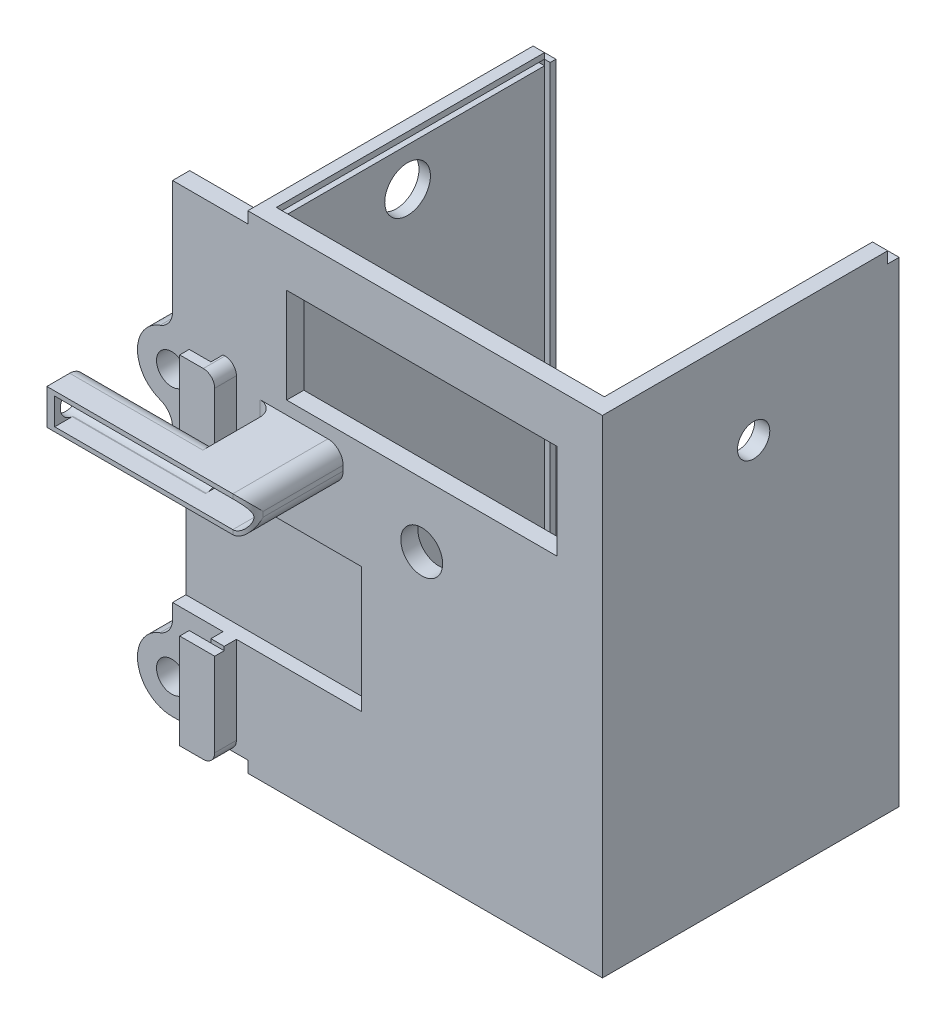
SolidWorks part; units mm, degrees
ref_plane "Alzado" through (0, 0, 0) normal (0, 0, 1) x (1, 0, 0)
ref_plane "Planta" through (0, 0, 0) normal (0, 1, 0) x (1, 0, 0)
ref_plane "Vista lateral" through (0, 0, 0) normal (1, 0, 0) x (0, 0, -1)
sketch "Croquis1" plane through (0, 0, 0) normal (0, 0, 1) x (1, 0, 0)
  circle A0 centre (-36.5282, 48.197) radius 4
  circle A1 centre (-36.5282, -21.803) radius 4
  circle A2 centre (-36.5282, 48.197) radius 9
  circle A3 centre (-36.5282, -21.803) radius 9
  dimension "D2" = 8
  dimension "D3" = 70
  dimension "D4" = 5
extrude "Saliente-Extruir1" add sketch "Croquis1" along normal blind 7
sketch "Croquis2" plane through (0, 0, 7) normal (0, 0, 1) x (1, 0, 0)
  line L0 (-18.6932, 21.2688) -> (-1.627, 21.2688) construction
  line L1 (-36.3068, 91.2688) -> (73.6932, 91.2688)
  line L2 (-36.3068, 91.2688) -> (-36.3068, -30.8003)
  line L3 (-36.3068, -30.8003) -> (73.6932, -30.8003)
  line L4 (73.6932, 91.2688) -> (73.6932, -30.8003)
  circle A2 centre (-36.5282, 48.197) radius 9
  circle A3 centre (-36.5282, -21.803) radius 9
  circle A4 centre (-36.5282, -21.803) radius 9 construction
  circle A5 centre (-36.5282, 48.197) radius 9 construction
  circle M7 centre (-36.5282, 48.197) radius 9
  dimension "D1" = 110
  dimension "D2" = 70
extrude "Saliente-Extruir2" add sketch "Croquis2" against normal blind 4.5 contours A3 L3 L4 L1 L2 M7
sketch "Croquis4" plane through (0, 0, 7) normal (0, 0, 1) x (1, 0, 0)
  line L1 (-23.0282, 58.197) -> (-19.5282, 58.197)
  line L2 (-23.0282, 58.197) -> (-23.0282, -30.8003)
  line L3 (-23.0282, -30.8003) -> (-19.5282, -30.8003)
  line L4 (-19.5282, 58.197) -> (-19.5282, -30.8003)
  line L5 (-36.3068, -30.8003) -> (73.6932, -30.8003) construction
  circle A0 centre (-36.5282, 48.197) radius 4 construction
  dimension "D2" = 10
  dimension "D1" = 13.5
  dimension "D4" = 3.5
extrude "Saliente-Extruir3" add sketch "Croquis4" along normal blind 3.2
sketch "Croquis3" plane through (0, 0, 7) normal (0, 0, 1) x (1, 0, 0)
  line L1 (-36.6357, 28.197) -> (13.3643, 28.197)
  line L2 (-36.6357, 28.197) -> (-36.6357, -4.803)
  line L3 (-36.6357, -4.803) -> (13.3643, -4.803)
  line L4 (13.3643, 28.197) -> (13.3643, -4.803)
  circle A0 centre (-36.5282, 48.197) radius 4 construction
  circle A2 centre (-36.5282, -21.803) radius 4 construction
  dimension "D3" = 50
  dimension "D1" = 17
  dimension "D2" = 20
extrude "Cortar-Extruir1" cut sketch "Croquis3" against normal blind 3.5 and the other way blind 13.5
sketch "Croquis5" plane through (0, 0, 10.2) normal (0, 0, 1) x (1, 0, 0)
  line L0 (-19.5282, -30.8003) -> (-19.5282, -4.803) construction
  line L1 (-28.7282, 58.197) -> (-19.5282, 58.197)
  line L2 (-28.7282, 58.197) -> (-28.7282, 29.197)
  line L3 (-28.7282, 29.197) -> (-19.5282, 29.197)
  line L4 (-19.5282, 58.197) -> (-19.5282, 29.197)
  line L5 (-28.7282, -5.803) -> (-19.5282, -5.803)
  line L6 (-28.7282, -5.803) -> (-28.7282, -30.8003)
  line L7 (-28.7282, -30.8003) -> (-19.5282, -30.8003)
  line L8 (-19.5282, -5.803) -> (-19.5282, -30.8003)
  line L10 (-23.0282, 28.197) -> (-36.3068, 28.197) construction
  line L11 (-36.3068, -4.803) -> (-23.0282, -4.803) construction
  line L12 (-23.0282, -30.8003) -> (-19.5282, -30.8003) construction
  line L16 (-19.5282, 58.197) -> (-23.0282, 58.197) construction
  dimension "D1" = 9.2
  dimension "D2" = 9.2
  dimension "D3" = 1
  dimension "D5" = 1
extrude "Saliente-Extruir4" add sketch "Croquis5" along normal blind 2.5
fillet "Redondeo1" radius 3 2 edges at (-19.5282, -30.8003, 9.85) (-19.5282, 58.197, 9.85)
fillet "Redondeo2" radius 5 2 edges at (-36.3068, -12.8057, 4.75) (-36.3068, 39.1997, 4.75)
sketch "Croquis6" plane through (0, 0, 7) normal (0, 0, 1) x (1, 0, 0)
  line L1 (-11.3068, 86.2688) -> (68.6932, 86.2688) construction
  line L2 (-11.3068, 86.2688) -> (-11.3068, 50.2688) construction
  line L3 (-11.3068, 50.2688) -> (68.6932, 50.2688) construction
  line L4 (68.6932, 86.2688) -> (68.6932, 50.2688) construction
  line L5 (-36.3068, 91.2688) -> (73.6932, 91.2688) construction
  line L11 (73.6932, 91.2688) -> (73.6932, -30.8003) construction
  line L13 (-6.3068, 81.2688) -> (64.6932, 81.2688)
  line L14 (-6.3068, 81.2688) -> (-6.3068, 56.2688)
  line L15 (-6.3068, 56.2688) -> (64.6932, 56.2688)
  line L16 (64.6932, 81.2688) -> (64.6932, 56.2688)
  point P13 (68.6932, 68.2688)
  dimension "D1" = 80
  dimension "D2" = 36
  dimension "D3" = 5
  dimension "D4" = 5
  dimension "D5" = 71
  dimension "D6" = 25
  dimension "D7" = 5
  dimension "D8" = 4
extrude "Cortar-Extruir2" cut sketch "Croquis6" against normal through all
sketch "Croquis7" plane through (0, 0, 0) normal (0, 0, -1) x (-1, 0, 0)
  line L0 (-64.6932, 56.2688) -> (-64.6932, 81.2688) construction
  line L1 (-68.1932, 75.7696) -> (-64.6932, 75.7696)
  line L2 (-68.1932, 75.7696) -> (-68.1932, 61.7696)
  line L3 (-68.1932, 61.7696) -> (-64.6932, 61.7696)
  line L4 (-64.6932, 75.7696) -> (-64.6932, 61.7696)
  dimension "D1" = 3.5
  dimension "D2" = 14
extrude "Cortar-Extruir3" cut sketch "Croquis7" against normal blind 5.5
sketch "Croquis8" plane through (0, 0, 0) normal (0, 0, -1) x (-1, 0, 0)
  line L0 (-64.6932, 81.2688) -> (6.3068, 81.2688) construction
  line L1 (-70.5004, 87.2688) -> (9.4996, 87.2688)
  line L2 (-70.5004, 87.2688) -> (-70.5004, 51.2688)
  line L3 (-70.5004, 51.2688) -> (9.4996, 51.2688)
  line L4 (9.4996, 87.2688) -> (9.4996, 51.2688)
  circle A0 centre (-68.5004, 85.2688) radius 1
  circle A1 centre (7.4996, 85.2688) radius 1
  circle A2 centre (7.4996, 53.2688) radius 1
  circle A3 centre (-68.5004, 53.2688) radius 1
  dimension "D4" = 2
  dimension "D5" = 2
  dimension "D6" = 2
  dimension "D1" = 36
  dimension "D2" = 80
  dimension "D3" = 6
  dimension "D7" = 2
  dimension "D8" = 2
extrude "Cortar-Extruir4" cut sketch "Croquis8" against normal blind 5 contours A0 | A1 | A2 | A3
sketch "Croquis9" plane through (73.6932, 0, 0) normal (1, 0, 0) x (0, 0, -1)
  line L0 (-7, 91.2688) -> (-7, -30.8003) construction
  line L1 (-7, 91.2688) -> (68, 91.2688)
  line L2 (-7, 91.2688) -> (-7, -30.8003)
  line L3 (-7, -30.8003) -> (68, -30.8003)
  line L4 (68, 91.2688) -> (68, -30.8003)
  line L5 (-2.5, 91.2688) -> (-7, 91.2688) construction
  line L6 (-2.5, -30.8003) -> (-7, -30.8003) construction
  dimension "D1" = 75
extrude "Saliente-Extruir5" add sketch "Croquis9" along normal blind 3 and the other way blind 1
sketch "Croquis10" plane through (0, -30.8003, 0) normal (0, -1, 0) x (1, 0, 0)
  line L0 (-22.5282, 7) -> (76.6932, 7) construction
  line L1 (-16.5282, 7) -> (-13.5282, 7)
  line L2 (-16.5282, 7) -> (-16.5282, -68)
  line L3 (-16.5282, -68) -> (-13.5282, -68)
  line L4 (-13.5282, 7) -> (-13.5282, -68)
  line L5 (-19.5282, 12.7) -> (-19.5282, 7) construction
  line L6 (76.6932, -68) -> (72.6932, -68) construction
  dimension "D1" = 3
  dimension "D2" = 3
extrude "Saliente-Extruir6" add sketch "Croquis10" against normal through all
sketch "Croquis11" plane through (0, -30.8003, 0) normal (0, -1, 0) x (1, 0, 0)
  line L1 (-16.5282, 7) -> (76.6932, 7)
  line L2 (-16.5282, 7) -> (-16.5282, -68)
  line L3 (-16.5282, -68) -> (76.6932, -68)
  line L4 (76.6932, 7) -> (76.6932, -68)
  line L5 (-22.5282, 7) -> (76.6932, 7) construction
  line L6 (-16.5282, 2.5) -> (-16.5282, -68) construction
extrude "Saliente-Extruir7" add sketch "Croquis11" along normal blind 3
sketch "Croquis12" plane through (72.6932, 0, 0) normal (-1, 0, 0) x (0, 0, 1)
  line L0 (-68, -30.8003) -> (-68, 91.2688) construction
  line L1 (-63, 43.1997) -> (-9, 43.1997) construction
  line L2 (-63, 43.1997) -> (-63, -25.8003) construction
  line L3 (-63, -25.8003) -> (-9, -25.8003) construction
  line L4 (-9, 43.1997) -> (-9, -25.8003) construction
  line L5 (2.5, -30.8003) -> (-68, -30.8003) construction
  circle A0 centre (-61, 29.1997) radius 2
  circle A1 centre (-11, 27.6997) radius 2
  circle A2 centre (-55, -23.8003) radius 2
  circle A3 centre (-27, -23.8003) radius 2
  circle A4 centre (-61, 29.1997) radius 1
  circle A5 centre (-11, 27.6997) radius 1
  circle A6 centre (-55, -23.8003) radius 1
  circle A7 centre (-27, -23.8003) radius 1
  dimension "D5" = 4
  dimension "D6" = 2
  dimension "D7" = 2
  dimension "D11" = 15.5
  dimension "D13" = 2
  dimension "D1" = 54
  dimension "D2" = 69
  dimension "D3" = 5
  dimension "D4" = 5
  dimension "D8" = 2
  dimension "D9" = 8
  dimension "D10" = 18
  dimension "D12" = 14
extrude "Saliente-Extruir8" add sketch "Croquis12" along normal blind 4
sketch "Croquis13" plane through (68.6932, 0, 0) normal (-1, 0, 0) x (0, 0, 1)
  circle A0 centre (-61, 29.1997) radius 1
  circle A1 centre (-11, 27.6997) radius 1
  circle A2 centre (-27, -23.8003) radius 1
  circle A3 centre (-55, -23.8003) radius 1
  circle A4 centre (-55, -23.8003) radius 1 construction
  circle A5 centre (-61, 29.1997) radius 1 construction
  circle A6 centre (-11, 27.6997) radius 1 construction
  circle A7 centre (-27, -23.8003) radius 1 construction
extrude "Cortar-Extruir6" cut sketch "Croquis13" against normal blind 6
sketch "Croquis14" plane through (72.6932, 0, 0) normal (-1, 0, 0) x (0, 0, 1)
  line L0 (-32.75, 91.2688) -> (-32.75, -24.8925) construction
  line L1 (-68, 91.2688) -> (2.5, 91.2688) construction
  line L2 (-72.5972, 68.7696) -> (5.5, 68.7696) construction
  line L3 (5.5, 75.7696) -> (5.5, 61.7696) construction
  circle A0 centre (-32.75, 68.7696) radius 4.25
  dimension "D1" = 8.5
extrude "Cortar-Extruir7" cut sketch "Croquis14" against normal through all
sketch "Croquis15" plane through (72.6932, 0, 0) normal (-1, 0, 0) x (0, 0, 1)
  line L1 (-26.3, 67.5196) -> (-26.3, 70.0196)
  line L2 (-26.3, 67.5196) -> (-27.5, 67.5196)
  line L3 (-27.5, 67.5196) -> (-27.5, 70.0196)
  line L4 (-26.3, 70.0196) -> (-27.5, 70.0196)
  line L6 (0.582, 68.7696) -> (-32.75, 68.7696) construction
  circle A0 centre (-32.75, 68.7696) radius 4.25 construction
  point P4 (0, 0)
  point P5 (0.3874, 67.4)
  point P10 (0, 0)
  point P11 (-38.3751, 75.0141)
  point P12 (-26.3, 68.7696)
  point P13 (-19.8399, 70.0196)
  point P14 (-23.3777, 67.8615)
  point P15 (-25.9157, 70.0919)
  point P16 (0, 0)
  dimension "D2" = 5.25
  dimension "D1" = 2.5
  dimension "D3" = 1.2
extrude "Cortar-Extruir8" cut sketch "Croquis15" against normal blind 1.5
sketch "Croquis16" plane through (0, 0, 7) normal (0, 0, 1) x (1, 0, 0)
  line L1 (-16.5282, 28.197) -> (-13.5282, 28.197)
  line L2 (-16.5282, 28.197) -> (-16.5282, -4.803)
  line L3 (-16.5282, -4.803) -> (-13.5282, -4.803)
  line L4 (-13.5282, 28.197) -> (-13.5282, -4.803)
extrude "Cortar-Extruir10" cut sketch "Croquis16" against normal blind 3.5
sketch "Croquis17" plane through (0, 0, 2.5) normal (0, 0, -1) x (-1, 0, 0)
  line L0 (36.3068, 91.2688) -> (36.3068, 57.1943) construction
  line L1 (16.5282, 61.1951) -> (36.3068, 61.1951)
  line L2 (16.5282, 61.1951) -> (16.5282, -30.8003)
  line L3 (16.5282, -30.8003) -> (36.3068, -30.8003)
  line L4 (36.3068, 61.1951) -> (36.3068, -30.8003)
  line L5 (36.3068, -30.8003) -> (16.5282, -30.8003) construction
  line L6 (16.5282, 91.2688) -> (16.5282, -33.8003) construction
  circle A0 centre (36.5282, 48.197) radius 13
  circle A1 centre (36.5282, -21.803) radius 13
  circle A2 centre (36.5282, 48.197) radius 9 construction
  circle A3 centre (36.5282, -21.803) radius 9 construction
  line M8 (16.5282, 91.2688) -> (16.5282, -30.8003)
  line M9 (16.5282, -30.8003) -> (36.3068, -30.8003)
  line M12 (36.3068, -8.6438) -> (36.3068, 35.0378)
  dimension "D1" = 26
extrude "Saliente-Extruir9" add sketch "Croquis17" along normal blind 4.5 contours A1 L4 A0 L1 M12 M8 M9
sketch "Croquis18" plane through (0, 0, 0) normal (0, 0, -1) x (-1, 0, 0)
  line L0 (36.3068, 61.1951) -> (36.3068, 35.1989)
  line L1 (36.3068, -8.8049) -> (36.3068, -30.8003)
  line L2 (27.1447, -30.8003) -> (36.3068, -30.8003)
  line L3 (36.3068, 91.2688) -> (36.3068, 61.1951) construction
  circle A0 centre (36.5282, 48.197) radius 13
  circle A1 centre (36.5282, -21.803) radius 13
  arc A2 (36.3068, -8.8049) -> (27.1447, -30.8003) centre (36.5282, -21.803) ccw construction
  arc A3 (36.3068, 61.1951) -> (36.3068, 35.1989) centre (36.5282, 48.197) ccw construction
  circle A4 centre (36.5282, 48.197) radius 4
  circle A5 centre (36.5282, -21.803) radius 4
  circle A6 centre (36.5282, -21.803) radius 4 construction
  circle A7 centre (36.5282, 48.197) radius 4 construction
  circle M6 centre (36.5282, -21.803) radius 9
extrude "Saliente-Extruir10" add sketch "Croquis18" against normal blind 3 contours A4 L0 A0 | L1 A1 L2 M6
fillet "Redondeo3" radius 5 11 edges at (-36.3068, 57.1943, 3.5) (-37.9786, 39.3146, 2.5) (-36.3068, -8.8049, -1) (-36.3068, 35.1989, -1) (-36.3068, 61.1951, 1.25) (-36.3068, 39.1997, 1.25) (-36.3068, 37.1993, 0) (-36.3068, 59.1947, 0) (-37.9786, -12.9207, 2.5) (-36.3068, -12.8057, 1.25) (-36.3068, -10.8053, 0)
fillet "Redondeo5" radius 5 1 edges at (-26.4188, 61.1951, 2.5)
sketch "Croquis19" plane through (0, 0, 2.5) normal (0, 0, -1) x (-1, 0, 0)
  line L1 (-29.1932, 81.2688) -> (-29.1932, -17.9377) construction
  line L2 (-64.6932, 81.2688) -> (6.3068, 81.2688) construction
  circle A0 centre (-29.1932, 39.4961) radius 5.5
  dimension "D1" = 11
extrude "Cortar-Extruir11" cut sketch "Croquis19" against normal blind 4.5
sketch "Croquis20" plane through (0, 0, -68) normal (0, 0, -1) x (-1, 0, 0)
  line L0 (13.5282, 91.2688) -> (-72.6932, 91.2688) construction
  line L1 (-75.1932, 91.2688) -> (-76.6932, 91.2688)
  line L2 (-75.1932, 91.2688) -> (-75.1932, -32.3003)
  line L3 (-75.1932, -32.3003) -> (-76.6932, -32.3003)
  line L4 (-76.6932, 91.2688) -> (-76.6932, -32.3003)
  line L5 (-76.6932, -32.3003) -> (16.5282, -32.3003)
  line L6 (-76.6932, -32.3003) -> (-76.6932, -33.8003)
  line L7 (-76.6932, -33.8003) -> (16.5282, -33.8003)
  line L8 (16.5282, -32.3003) -> (16.5282, -33.8003)
  line L9 (15.0282, -33.8003) -> (16.5282, -33.8003)
  line L10 (15.0282, -33.8003) -> (15.0282, 91.2688)
  line L11 (15.0282, 91.2688) -> (16.5282, 91.2688)
  line L12 (16.5282, -33.8003) -> (16.5282, 91.2688)
  line L13 (-76.6932, -33.8003) -> (-76.6932, 91.2688) construction
  line L14 (16.5282, -33.8003) -> (-76.6932, -33.8003) construction
  line L15 (16.5282, 61.1951) -> (16.5282, -30.8003) construction
  line M17 (16.5282, -33.8003) -> (16.5282, 91.2688)
  line M18 (16.5282, 91.2688) -> (13.5282, 91.2688)
  dimension "D1" = 1.5
  dimension "D2" = 1.5
  dimension "D3" = 1.5
extrude "Saliente-Extruir11" add sketch "Croquis20" along normal blind 1.5 contours L10 L5 M17 M18 | L4 L3 L2 L1
sketch "Croquis21" plane through (0, 0, -69.5) normal (0, 0, -1) x (-1, 0, 0)
  line L0 (13.5282, -30.8003) -> (13.5282, 91.2688) construction
  line L1 (-76.6932, 91.2688) -> (-72.6932, 91.2688)
  line L2 (-76.6932, 91.2688) -> (-76.6932, -33.8003)
  line L3 (-76.6932, -33.8003) -> (-72.6932, -33.8003)
  line L4 (-72.6932, 91.2688) -> (-72.6932, -33.8003)
  line L5 (-72.6932, -33.8003) -> (13.5282, -33.8003)
  line L6 (-72.6932, -33.8003) -> (-72.6932, -30.8003)
  line L7 (-72.6932, -30.8003) -> (13.5282, -30.8003)
  line L8 (13.5282, -33.8003) -> (13.5282, -30.8003)
  line L9 (16.5282, -33.8003) -> (13.5282, -33.8003)
  line L10 (16.5282, -33.8003) -> (16.5282, 91.2688)
  line L11 (16.5282, 91.2688) -> (13.5282, 91.2688)
  line L12 (13.5282, -33.8003) -> (13.5282, 91.2688)
  line L13 (16.5282, 61.1951) -> (16.5282, -30.8003) construction
  line L14 (13.5282, -30.8003) -> (-72.6932, -30.8003) construction
  line L15 (-76.6932, -33.8003) -> (16.5282, -33.8003) construction
  line L18 (-72.6932, -30.8003) -> (-72.6932, 91.2688) construction
  line L19 (-76.6932, 91.2688) -> (-76.6932, -33.8003) construction
  line L20 (13.5282, 91.2688) -> (-72.6932, 91.2688) construction
  line M14 (15.0282, -32.3003) -> (-75.1932, -32.3003)
  line M15 (-75.1932, -32.3003) -> (-75.1932, 91.2688)
  line M16 (-75.1932, 91.2688) -> (-76.6932, 91.2688)
  line M17 (-76.6932, 91.2688) -> (-76.6932, -33.8003)
  line M18 (-76.6932, -33.8003) -> (16.5282, -33.8003)
extrude "Saliente-Extruir12" add sketch "Croquis21" along normal blind 1.5 contours L4 L1 M15 M14 | L4 M14 M15 M16 M17 M18 | L8 L7 L4 M14 | L8 L4 M18 M14 | L12 L11 L10 L9
sketch "Croquis22" plane through (0, 91.2688, 0) normal (0, 1, 0) x (1, 0, 0)
  line L0 (75.1932, 68) -> (72.6932, 68) construction
  line L1 (-16.5282, 68) -> (-15.0282, 68)
  line L2 (-16.5282, 68) -> (-16.5282, -5)
  line L3 (-16.5282, -5) -> (-15.0282, -5)
  line L4 (-15.0282, 68) -> (-15.0282, -5)
  line L5 (-16.5282, -5) -> (76.6932, -5)
  line L6 (-16.5282, -5) -> (-16.5282, -7)
  line L7 (-16.5282, -7) -> (76.6932, -7)
  line L8 (76.6932, -5) -> (76.6932, -7)
  line L9 (76.6932, -5) -> (75.1932, -5)
  line L10 (76.6932, -5) -> (76.6932, 68)
  line L11 (76.6932, 68) -> (75.1932, 68)
  line L12 (75.1932, -5) -> (75.1932, 68)
  line L13 (75.1932, 68) -> (-15.0282, 68) construction
  line L14 (-16.5282, -2.5) -> (-16.5282, 71) construction
  line L15 (76.6932, 71) -> (76.6932, -7) construction
  line L19 (-36.3068, -7) -> (76.6932, -7) construction
  line M20 (-16.5282, 71) -> (-16.5282, -2.5)
  line M23 (-36.3068, -7) -> (76.6932, -7)
  line M24 (76.6932, -7) -> (76.6932, 71)
  dimension "D1" = 2
  dimension "D2" = 1.5
  dimension "D3" = 1.5
extrude "Saliente-Extruir13" add sketch "Croquis22" along normal blind 1.5 contours L4 L1 L2 L3 M20 | L3 L6 L5 M23 M24 | L10 L11 L12 L9
sketch "Croquis23" plane through (0, 92.7688, 0) normal (0, 1, 0) x (1, 0, 0)
  line L1 (-16.5282, 68) -> (-13.5282, 68)
  line L2 (-16.5282, 68) -> (-16.5282, -2.5)
  line L3 (-16.5282, -2.5) -> (-13.5282, -2.5)
  line L4 (-13.5282, 68) -> (-13.5282, -2.5)
  line L5 (-16.5282, -2.5) -> (76.6932, -2.5)
  line L6 (-16.5282, -2.5) -> (-16.5282, -7)
  line L7 (-16.5282, -7) -> (76.6932, -7)
  line L8 (76.6932, -2.5) -> (76.6932, -7)
  line L9 (76.6932, -2.5) -> (72.6932, -2.5)
  line L10 (76.6932, -2.5) -> (76.6932, 68)
  line L11 (76.6932, 68) -> (72.6932, 68)
  line L12 (72.6932, -2.5) -> (72.6932, 68)
  line L13 (-13.5282, -2.5) -> (72.6932, -2.5) construction
  line L14 (-16.5282, 68) -> (-16.5282, -7) construction
  line L15 (-13.5282, 68) -> (-13.5282, -2.5) construction
  line L16 (-13.5282, 68) -> (72.6932, 68) construction
  line M13 (-15.0282, -5) -> (-15.0282, 68)
  line M14 (-15.0282, 68) -> (-16.5282, 68)
  line M15 (-16.5282, 68) -> (-16.5282, -7)
  line M17 (76.6932, -7) -> (76.6932, 68)
  line M18 (76.6932, 68) -> (75.1932, 68)
  line M19 (75.1932, 68) -> (75.1932, -5)
extrude "Saliente-Extruir14" add sketch "Croquis23" along normal blind 1.5 contours L4 L1 L3 M13 | L3 M15 M13 M14 | L12 L5 L11 M19 | L5 M19 M17 M18
sketch "Croquis26" plane through (0, 0, 7) normal (0, 0, 1) x (1, 0, 0)
  line L0 (-36.5282, 48.197) -> (29.9581, 48.197) construction
  line L2 (-9.3505, 52.8575) -> (8.528, 52.8575)
  line L3 (-9.3505, 52.8575) -> (-9.3505, 43.5364)
  line L4 (-9.3505, 43.5364) -> (8.528, 43.5364)
  line L5 (8.528, 52.8575) -> (8.528, 43.5364)
  circle A2 centre (-36.5282, 48.197) radius 4 construction
  point P2 (-9.3505, 48.197)
extrude "Saliente-Extruir15" add sketch "Croquis26" along normal blind 25
sketch "Croquis27" plane through (-9.3505, 0, 0) normal (-1, 0, 0) x (0, 0, 1)
  line L0 (32, 43.5364) -> (7, 43.5364) construction
  line L1 (22, 52.8575) -> (32, 52.8575)
  line L2 (22, 52.8575) -> (22, 43.5364)
  line L3 (22, 43.5364) -> (32, 43.5364)
  line L4 (32, 52.8575) -> (32, 43.5364)
  dimension "D1" = 10
extrude "Saliente-Extruir16" add sketch "Croquis27" along normal blind 35
fillet "Redondeo6" radius 4 6 edges at (-26.8505, 43.5364, 22) (-26.8505, 52.8575, 22) (-9.3505, 48.197, 7) (8.528, 43.5364, 19.5) (8.528, 52.8575, 19.5) (8.528, 48.197, 32)
sketch "Croquis28" plane through (0, 0, 32) normal (0, 0, 1) x (1, 0, 0)
  line L1 (-7.2874, 51.697) -> (4.528, 51.697)
  line L2 (-7.2874, 51.697) -> (-7.2874, 44.697)
  line L3 (-7.2874, 44.697) -> (4.528, 44.697)
  line L4 (4.528, 51.697) -> (4.528, 44.697)
  line L6 (4.528, 43.5364) -> (4.528, 52.8575) construction
  circle A0 centre (4.528, 48.197) radius 3.5
  line M7 (4.528, 43.5364) -> (4.528, 52.8575)
  dimension "D1" = 7
extrude "Cortar-Extruir12" cut sketch "Croquis28" against normal blind 32 and the other way blind 10 contours A0 L1 L2 L3 | A0 M7 | A0 M7
sketch "Croquis29" plane through (-7.2874, 0, 0) normal (1, 0, 0) x (0, 0, -1)
  line L1 (-32, 51.697) -> (-27.4063, 51.697)
  line L2 (-32, 51.697) -> (-32, 44.697)
  line L3 (-32, 44.697) -> (-27.4063, 44.697)
  line L4 (-27.4063, 51.697) -> (-27.4063, 44.697)
  line L5 (-32, 44.697) -> (-2.5, 44.697) construction
  line L7 (-32, 51.697) -> (-2.5, 51.697) construction
  circle A0 centre (-27.4063, 48.197) radius 3.5
  line M9 (-2.5, 51.697) -> (-32, 51.697)
  line M10 (-32, 51.697) -> (-32, 44.697)
  line M11 (-32, 44.697) -> (-2.5, 44.697)
extrude "Cortar-Extruir13" cut sketch "Croquis29" against normal blind 35 contours A0 M9 M10 M11 | L4 A0 | L4 A0
sketch "Croquis31" plane through (-44.3505, 0, 0) normal (-1, 0, 0) x (0, 0, 1)
  line L0 (2.3134, 48.197) -> (32, 48.197) construction
  line L1 (32, 43.5364) -> (32, 52.8575) construction
  circle A0 centre (27.0394, 48.197) radius 3.5
  dimension "D1" = 7
extrude "Cortar-Extruir14" cut sketch "Croquis31" against normal blind 38
sketch "Croquis32" plane through (-16.5282, 0, 0) normal (-1, 0, 0) x (0, 0, 1)
  line L0 (-84.2932, 48.197) -> (0, 48.197) construction
  line L1 (0, 61.1951) -> (0, 35.1988) construction
  line L2 (-32, -33.8003) -> (-32, 108.5296) construction
  line L3 (7, -33.8003) -> (-71, -33.8003) construction
  circle A0 centre (-32, 81.197) radius 6
  dimension "D1" = 12
  dimension "D2" = 33
extrude "Cortar-Extruir15" cut sketch "Croquis32" against normal blind 4
sketch "Croquis33" plane through (0, 0, 2.5) normal (0, 0, -1) x (-1, 0, 0)
  line L1 (-35.9854, 88.2844) -> (3.7097, 88.2844)
  line L2 (-35.9854, 88.2844) -> (-35.9854, 83.0981)
  line L3 (-35.9854, 83.0981) -> (3.7097, 83.0981)
  line L4 (3.7097, 88.2844) -> (3.7097, 83.0981)
extrude "Cortar-Extruir16" cut sketch "Croquis33" against normal blind 1
